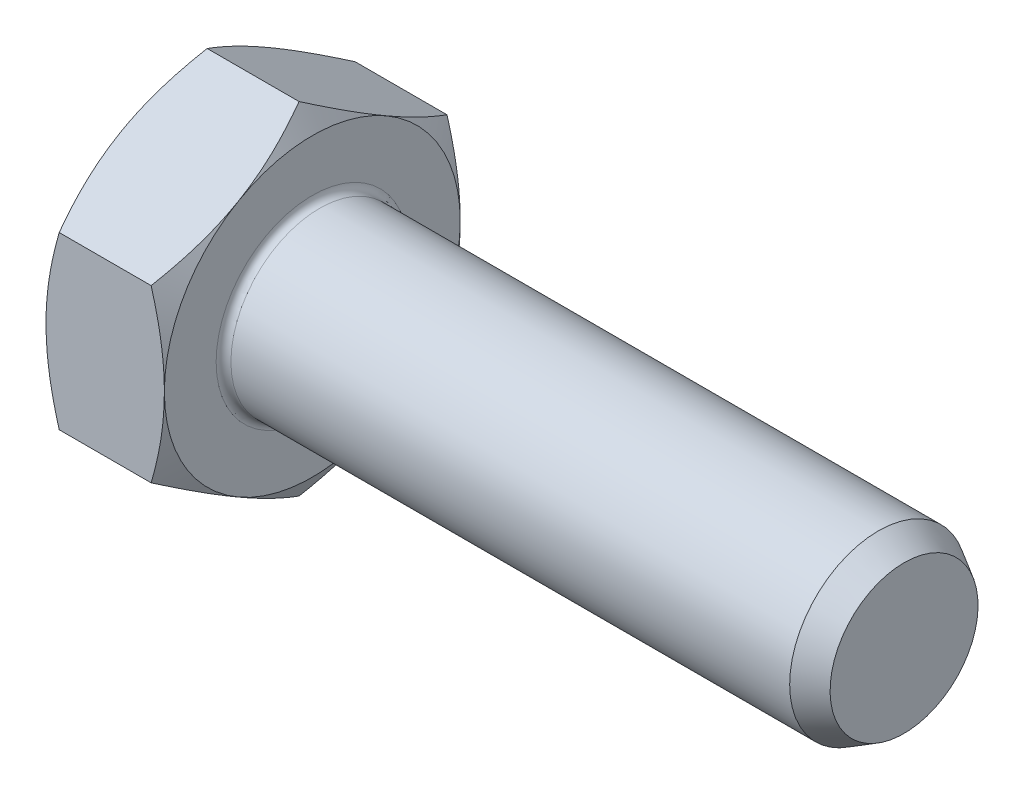
SolidWorks part; units mm, degrees
ref_plane "Front" through (0, 0, 0) normal (0, 0, 1) x (1, 0, 0)
ref_plane "Top" through (0, 0, 0) normal (0, 1, 0) x (1, 0, 0)
ref_plane "Right" through (0, 0, 0) normal (1, 0, 0) x (0, 0, -1)
sketch "Sketch2" plane through (0, 0, 0) normal (1, 0, 0) x (0, 0, -1)
  line L1 (0, 5.7735) -> (-5, 2.8868)
  line L2 (-5, 2.8868) -> (-5, -2.8868)
  line L3 (-5, -2.8868) -> (0, -5.7735)
  line L4 (0, -5.7735) -> (5, -2.8868)
  line L5 (5, -2.8868) -> (5, 2.8868)
  line L6 (5, 2.8868) -> (0, 5.7735)
  circle A0 centre (0, 0) radius 5 construction
extrude "BaseHead" add sketch "Sketch2" along normal blind 4
sketch "Sketch1" plane through (0, 0, 0) normal (0, 0, 1) x (1, 0, 0)
  line L0 (-14.1054, 0) -> (35.3165, 0) construction
  line L1 (24, 0) -> (24, 3)
  line L2 (24, 3) -> (4, 3)
  line L3 (4, 3) -> (4, 0)
  line L4 (24, 0) -> (4, 0)
  line L5 (4, 2.8868) -> (4, -2.8868) construction
  dimension "l" = 20
revolve "BaseBody" add sketch "Sketch1" angle 360 about L0
cosmetic thread "ThreadCosmetic1" [suppressed] parameters "D2"=5
fillet "Fillet2" radius 0.25 1 edges at (4, 0, 3)
sketch "Sketch3" plane through (0, 0, 0) normal (0, 0, 1) x (1, 0, 0)
  line L0 (4.4119, 0) -> (11.0765, 0) construction
  line L2 (2, 5.7735) -> (2, -5.7735) construction
  line L5 (0, 5.7735) -> (0.4466, 5.7735)
  line L6 (0.4466, 5.7735) -> (0, 5)
  line L8 (0, 5) -> (0, 5.7735)
  line L9 (4, 5) -> (4, 5.7735)
  line L10 (3.5534, 5.7735) -> (4, 5)
  line L11 (4, 5.7735) -> (3.5534, 5.7735)
  dimension "D1" = 10
  dimension "D2" = 30
revolve "Cut-Revolve3" cut sketch "Sketch3" angle 360 about L0
sketch "Sketch4" plane through (0, 0, 0) normal (0, 0, 1) x (1, 0, 0)
  line L0 (25.3282, 0) -> (10.3612, 0) construction
  line L2 (23.134, -3) -> (24, -2.5)
  line L4 (24, -3) -> (24, 3) construction
  line L6 (24, -2.5) -> (24, -3)
  line L7 (24, -3) -> (23.134, -3)
  dimension "D1" = 30
  dimension "D2" = 5
  dimension "D3" = 6
revolve "Cut-Revolve1" cut sketch "Sketch4" angle 360 about L0
sketch "Sketch6" plane through (0, 0, 0) normal (0, 0, 1) x (1, 0, 0)
  line L0 (0, 0) -> (2.935, 0) construction
  line L1 (0, 0) -> (0.8, 0)
  line L2 (0, 0) -> (0, 4.1667)
  line L3 (0, 4.1667) -> (0.8, 4.1667)
  line L4 (0.8, 0) -> (0.8, 4.1667)
  dimension "D1" = 0.8
  dimension "D2" = 8.3333
revolve "Cut-Revolve4" cut sketch "Sketch6" angle 360 about L0
sketch "Sketch7" plane through (0, 0, 0) normal (0, 0, 1) x (1, 0, 0)
  line L0 (0, 0) -> (24.3746, 0) construction
  line L1 (22.8453, 3.5774) -> (23.4226, 3.5774)
  line L2 (23.4226, 3.5774) -> (23.4226, 3)
  line L3 (23.4226, 3) -> (23.134, 2.5)
  line L4 (23.134, 2.5) -> (22.8453, 3)
  line L5 (22.8453, 3) -> (22.8453, 3.5774)
  line L6 (23.134, 3) -> (23.134, -3) construction
  dimension "D1" = 6
  dimension "D2" = 2.5
revolve "Cut-Revolve10" [suppressed] cut sketch "Sketch7" angle 360 about L0
pattern_linear "LPattern10" [suppressed] count 26 spacing 0.75 along (-1, 0, 0) of bodies 108
sketch "Sketch5" plane through (0, 0, 0) normal (0, 1, 0) x (1, 0, 0)
  line L0 (18.0155, 0) -> (2.4696, 0) construction
  line L1 (4, -2.5) -> (4, 2.5) construction
  line L2 (4, 2.5) -> (12.8873, 2.5)
  line L3 (12.8873, 2.5) -> (14.1774, 3)
  line L4 (24, -2.5) -> (24, 2.5) construction
  line L5 (14.1774, 3) -> (4, 3)
  line L6 (4, 3) -> (4, 2.5)
  dimension "D1" = 2.5
  dimension "D2" = 6
  dimension "b" = 9.8226
  dimension "D3" = 20
revolve "Cut-Revolve2" [suppressed] cut sketch "Sketch5" angle 360 about L0
fillet "Fillet3" [suppressed] radius 0.25
equation "\"D2@ThreadCosmetic1\" = \"d@Sketch1\" - 1"
equation "\"D2@Sketch4\" = \"D2@ThreadCosmetic1\""
equation "\"D3@Sketch4\" = \"d@Sketch1\""
equation "\"D2@Sketch5\" = \"d@Sketch1\""
equation "\"D3@Sketch5\" = \"l@Sketch1\""
equation "\"D1@Sketch3\" = \"s@Sketch2\""
equation "\"D1@Sketch5\" = \"D2@Sketch5\" / 2 - 0.5"
equation "\"D1@Sketch6\" = \"k@BaseHead\" / 5"
equation "\"D2@Sketch6\" = \"s@Sketch2\" * 5 / 6"
equation "\"D1@Sketch7\" = \"d@Sketch1\""
equation "\"D2@Sketch7\" = \"D2@Sketch5\" / 2 - 0.5"
equation "\"D3@LPattern10\" = (  \"D1@Sketch7\" / 2 - \"D2@Sketch7\" )  * 1.5"
equation "\"D1@LPattern10\" = (  \"l@Sketch1\" - (  \"D3@Sketch4\" - \"D2@Sketch4\" )  / 2 * 1.732 )  / \"D3@LPattern10\""
